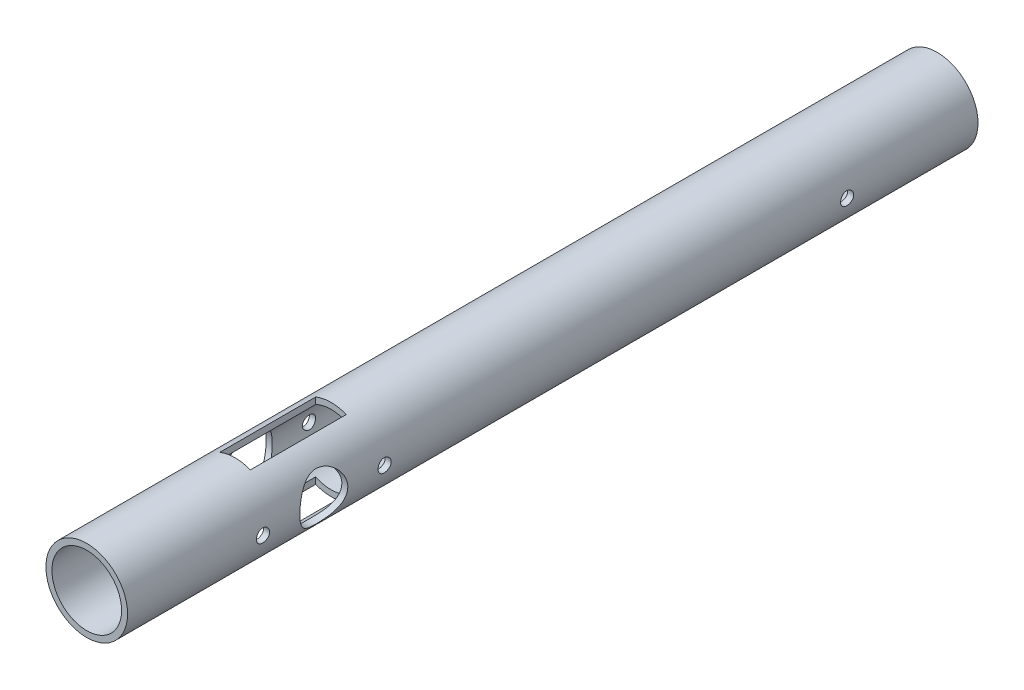
SolidWorks part; units mm, degrees
material "6061-T4 (SS)"
ref_plane "Front" through (0, 0, 0) normal (0, 0, 1) x (1, 0, 0)
ref_plane "Top" through (0, 0, 0) normal (0, 1, 0) x (1, 0, 0)
ref_plane "Right" through (0, 0, 0) normal (1, 0, 0) x (0, 0, -1)
sketch "Sketch1" plane through (0, 0, 0) normal (0, 0, 1) x (1, 0, 0)
  circle A0 centre (0, 0) radius 9.36
  circle A1 centre (0, 0) radius 7.99
extrude "Extrude1" add sketch "Sketch1" along normal blind 195
sketch "Sketch2" plane through (0, 0, 0) normal (1, 0, 0) x (0, 0, -1)
  line L0 (-30, -47.5362) -> (-30, 39.1475) construction
  line L1 (0, -9.36) -> (0, 9.36) construction
  line L2 (-150, -93.5027) -> (-150, 51.4365) construction
  line L3 (-195, 9.36) -> (-195, -9.36) construction
  circle A0 centre (-30, 0) radius 1.5
  circle A1 centre (-150, 0) radius 5.5
  circle A2 centre (-136.0625, 0) radius 1.5
  circle A3 centre (-163.9375, 0) radius 1.5
  point P10 (-163.9375, 0)
  point P11 (-136.0625, 0)
  point P16 (-195, 0)
  dimension "D2" = 150
  dimension "D3" = 13.9375
  dimension "D5" = 31.0625
  dimension "D1" = 30
  dimension "D4" = 13.9375
extrude "Extrude2" cut sketch "Sketch2" against normal through all and the other way through all
sketch "Sketch3" plane through (0, 0, 0) normal (0, 1, 0) x (1, 0, 0)
  line L0 (-54.8402, -150) -> (72.4613, -150) construction
  line L1 (7.99, 0) -> (-7.99, 0) construction
  line L2 (-44.3384, -139) -> (38.4408, -139) construction
  line L3 (-76.6388, -161) -> (67.6466, -161) construction
  line L4 (3.5, -160.8387) -> (3.5, -87.3966) construction
  line L5 (0, -179.9469) -> (0, -88.7091) construction
  line L6 (-3.5, -169.4108) -> (-3.5, -98.3485) construction
  line L8 (-3.5, -139) -> (3.5, -139)
  line L9 (-3.5, -139) -> (-3.5, -161)
  line L10 (-3.5, -161) -> (3.5, -161)
  line L11 (3.5, -139) -> (3.5, -161)
  dimension "D1" = 150
  dimension "D2" = 11
  dimension "D3" = 22
  dimension "D4" = 3.5
  dimension "D5" = 7
extrude "Extrude3" cut sketch "Sketch3" against normal blind 25 and the other way blind 25
